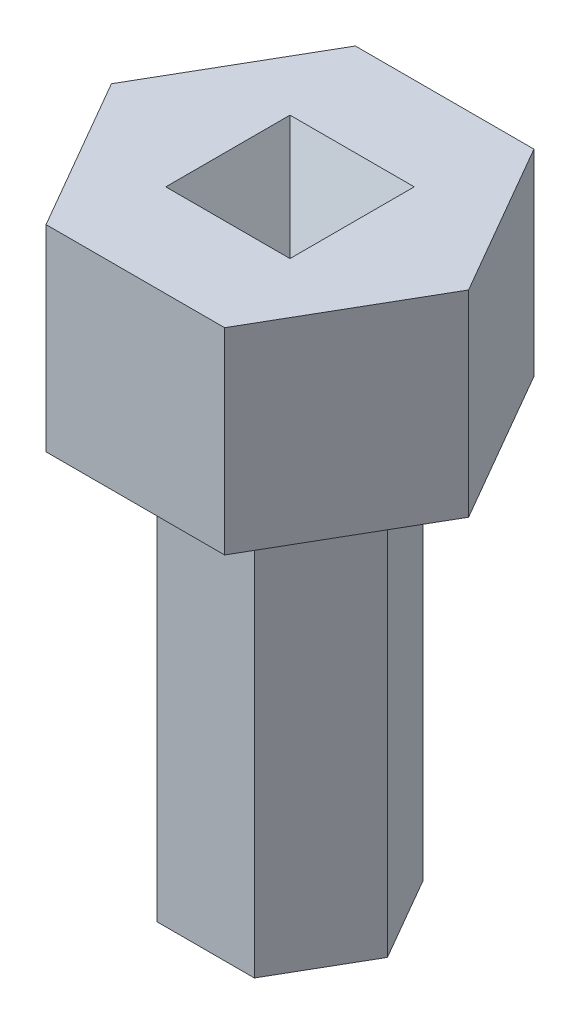
SolidWorks part; units mm, degrees
ref_plane "正面" through (0, 0, 0) normal (0, 0, 1) x (1, 0, 0)
ref_plane "平面" through (0, 0, 0) normal (0, 1, 0) x (1, 0, 0)
ref_plane "右側面" through (0, 0, 0) normal (1, 0, 0) x (0, 0, -1)
other "重心"
sketch "ｽｹｯﾁ1" plane through (0, 0, 0) normal (0, 1, 0) x (1, 0, 0)
  line L1 (3.4641, -6) -> (6.9282, 0)
  line L2 (6.9282, 0) -> (3.4641, 6)
  line L3 (3.4641, 6) -> (-3.4641, 6)
  line L4 (-3.4641, 6) -> (-6.9282, 0)
  line L5 (-6.9282, 0) -> (-3.4641, -6)
  line L6 (-3.4641, -6) -> (3.4641, -6)
  circle A0 centre (0, 0) radius 6 construction
  dimension "D1" = 12
extrude "ﾎﾞｽ - 押し出し1" add sketch "ｽｹｯﾁ1" along normal blind 30
sketch "ｽｹｯﾁ2" plane through (0, 30, 0) normal (0, 1, 0) x (1, 0, 0)
  line L1 (6.3509, -11) -> (12.7017, 0)
  line L2 (12.7017, 0) -> (6.3509, 11)
  line L3 (6.3509, 11) -> (-6.3509, 11)
  line L4 (-6.3509, 11) -> (-12.7017, 0)
  line L5 (-12.7017, 0) -> (-6.3509, -11)
  line L6 (-6.3509, -11) -> (6.3509, -11)
  circle A0 centre (0, 0) radius 11 construction
  dimension "D1" = 22
extrude "ﾎﾞｽ - 押し出し2" add sketch "ｽｹｯﾁ2" along normal blind 14
sketch "ｽｹｯﾁ3" plane through (0, 44, 0) normal (0, 1, 0) x (1, 0, 0)
  line L0 (-12.7017, 0) -> (12.7017, 0) construction
  line L1 (0, 11) -> (0, -11) construction
  line L2 (6.3509, 11) -> (-6.3509, 11) construction
  line L3 (-6.3509, -11) -> (6.3509, -11) construction
  line L4 (0, -0.05) -> (0, 0.05) construction
  line L5 (-0.05, 0.05) -> (0.05, 0.05)
  line L6 (-0.05, 0.05) -> (-0.05, -0.05)
  line L7 (-0.05, -0.05) -> (0.05, -0.05)
  line L8 (0.05, 0.05) -> (0.05, -0.05)
  line L9 (0.05, 0) -> (-0.05, 0) construction
  dimension "D1" = 0.1
extrude "ｶｯﾄ - 押し出し1" cut sketch "ｽｹｯﾁ3" against normal blind 12
chamfer "面取り1" distance 12 angle 20 4 edges at (0, 44, 0.05) (-0.05, 44, 0) (0, 44, -0.05) (0.05, 44, 0) first distance on face at (0, 38, 0.05) first distance on face at (-0.05, 38, 0) first distance on face at (0, 38, -0.05) first distance on face at (0.05, 38, 0)
ref_plane "平面1" through (0, 0, 0) normal (0.866, 0, 0.5) x (0.5, 0, -0.866)
ref_plane "平面2" through (0, 0, 0) normal (0, 0, 1) x (1, 0, 0)
ref_axis "軸1" through (0, 31.5, 0) along (0, -1, 0)
